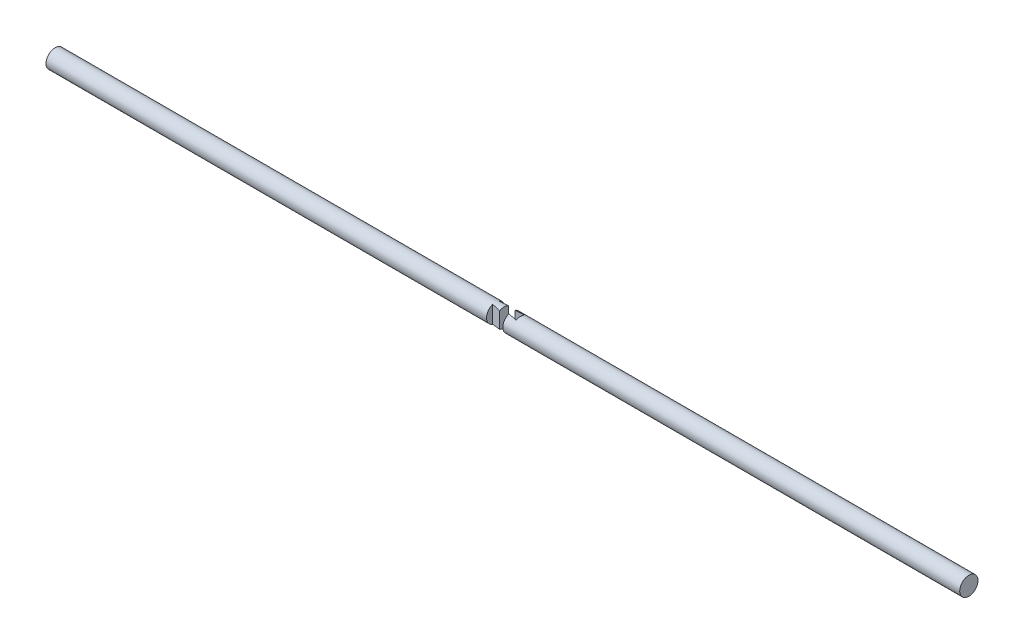
SolidWorks part; units mm, degrees
ref_plane "Front Plane" through (0, 0, 0) normal (0, 0, 1) x (1, 0, 0)
ref_plane "Top Plane" through (0, 0, 0) normal (0, 1, 0) x (1, 0, 0)
ref_plane "Right Plane" through (0, 0, 0) normal (1, 0, 0) x (0, 0, -1)
sketch "Sketch1" plane through (0, 0, 0) normal (1, 0, 0) x (0, 0, -1)
  circle A0 centre (0, 0) radius 4
  dimension "D1" = 8
extrude "Boss-Extrude1" add sketch "Sketch1" along normal blind 400
sketch "Sketch2" plane through (0, 0, 0) normal (0, 1, 0) x (1, 0, 0)
  line L0 (199.9857, 1.3) -> (200, 4)
  line L1 (199.9857, 1.3) -> (203.7287, 1.96)
  line L2 (203.7287, 1.96) -> (203.7287, -1.96)
  line L3 (203.7287, -1.96) -> (199.9857, -1.3)
  line L4 (199.9857, -1.3) -> (200, -4)
  line L5 (0, -4) -> (400, -4) construction
  line L6 (400, 4) -> (0, 4) construction
  line L7 (203.7287, 1.96) -> (203.7287, 4) construction
  line L8 (203.7287, -1.96) -> (203.7287, -4) construction
  line L9 (199.9857, 1.3) -> (202.1778, 1.3) construction
  line L10 (199.9857, -1.3) -> (202.5511, -1.3) construction
  line L11 (192.8374, 1.3) -> (192.8516, 4)
  line L12 (192.8374, 1.3) -> (196.5803, 1.96)
  line L13 (196.5803, 1.96) -> (196.5803, -1.96)
  line L14 (192.8374, -1.3) -> (192.8517, -4)
  line L15 (196.5803, -1.96) -> (192.8374, -1.3)
  line L16 (192.8516, 4) -> (200, 4)
  line L17 (192.8517, -4) -> (200, -4)
  line L18 (191.0267, 4) -> (191.0267, -4) construction
  line L19 (191.0267, 0) -> (205.857, 0) construction
  line L20 (203.7287, 1.96) -> (199.6033, 0) construction
  line L21 (199.6033, 0) -> (203.7287, -1.96) construction
  point P24 (196.5803, 0)
  point P27 (203.7287, 0)
  dimension "D1" = 10
  dimension "D2" = 10
  dimension "D3" = 2.7
extrude "Cut-Extrude3" cut sketch "Sketch2" against normal through all both and the other way through all
split "Split1" bodies to split 106 107 resulting bodies 108 109
equation "\"Axle_length\"= 300mm"
equation "\"axle_diametet\"=5"
